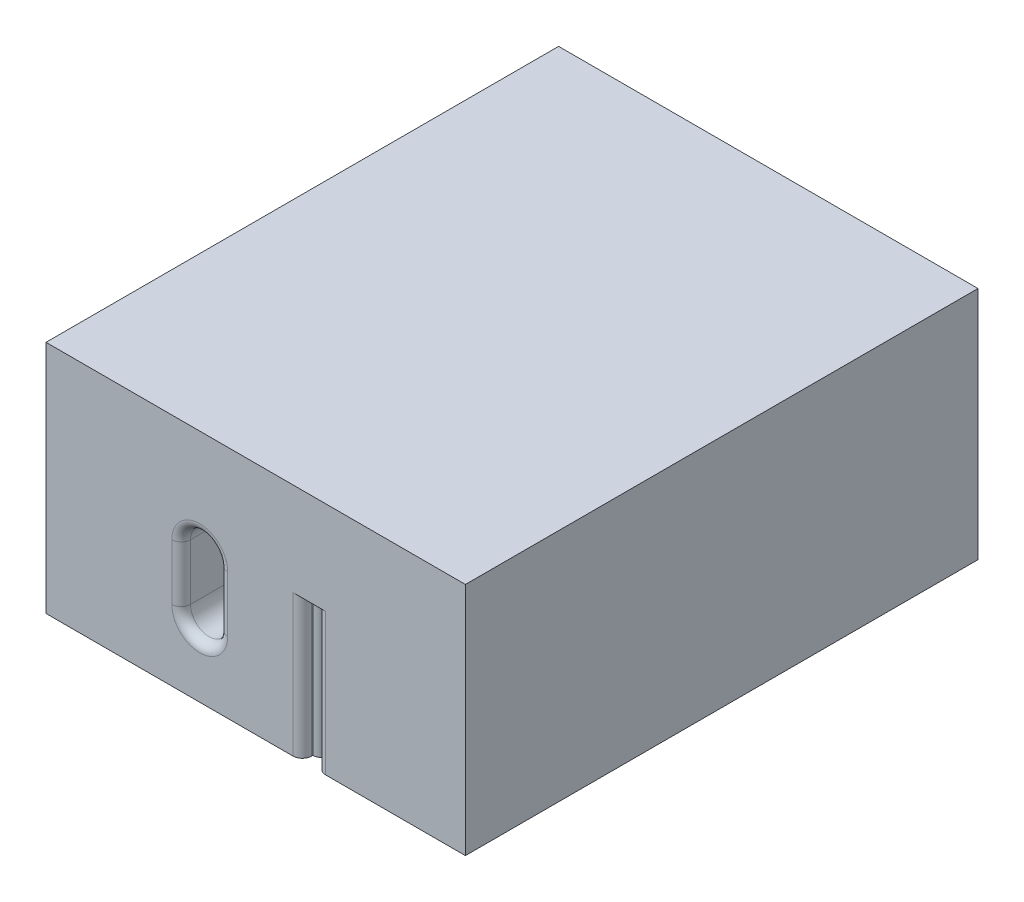
SolidWorks part; units mm, degrees
material "ABS"
ref_plane "Plan de face" through (0, 0, 0) normal (0, 0, 1) x (1, 0, 0)
ref_plane "Plan de dessus" through (0, 0, 0) normal (0, 1, 0) x (1, 0, 0)
ref_plane "Plan de droite" through (0, 0, 0) normal (1, 0, 0) x (0, 0, -1)
sketch "Esquisse1" plane through (0, 0, 0) normal (0, 0, 1) x (1, 0, 0)
  line L0 (0, 0) -> (0, 10) construction
  line L1 (-22.5, -10.6) -> (22.5, -10.6)
  line L2 (-22.5, 14.6) -> (22.5, 14.6)
  line L3 (-15.3167, 7.6) -> (-4, 7.6) construction
  line L4 (-2, 5.6) -> (-2, -5.6) construction
  line L5 (-4, -7.6) -> (-15.3167, -7.6) construction
  line L6 (-6, 3) -> (-6, -3) construction
  line L7 (-4, 3) -> (-4, -3)
  line L8 (-8, 3) -> (-8, -3)
  line L9 (22.5, -10.6) -> (22.5, 14.6)
  line L10 (-22.5, -10.6) -> (-22.5, 14.6)
  arc A4 (-15.6723, 6.7485) -> (-15.6723, -6.7485) centre (-22.5, 0) cw construction
  arc A5 (-15.3167, -7.6) -> (-15.6723, -6.7485) centre (-15.3167, -7.1) cw construction
  arc A6 (-15.3167, 7.6) -> (-15.6723, 6.7485) centre (-15.3167, 7.1) ccw construction
  arc A7 (-2, -5.6) -> (-4, -7.6) centre (-4, -5.6) cw construction
  arc A8 (-4, 7.6) -> (-2, 5.6) centre (-4, 5.6) cw construction
  arc A9 (-4, 3) -> (-8, 3) centre (-6, 3) ccw
  arc A10 (-8, -3) -> (-4, -3) centre (-6, -3) ccw
  point P18 (-16.6348, -7.6)
  point P21 (-16.6348, 7.6)
  point P28 (-6, 0)
  dimension "D2" = 25.2
  dimension "D6" = 7
  dimension "D8" = 0.5
  dimension "D9" = 2
  dimension "D3" = 10
  dimension "D4" = 45
  dimension "D7" = 2
  dimension "D10" = 6
  dimension "D11" = 4
  dimension "D12" = 6
extrude "Boss.-Extru.1" add sketch "Esquisse1" along normal blind 55
sketch "Esquisse3" plane through (0, -10.6, 0) normal (0, -1, 0) x (1, 0, 0)
  line L0 (5, 55) -> (5, 39.4854)
  line L2 (-22.5, 55) -> (22.5, 55) construction
  line L3 (4.4668, 36.6136) -> (0.5332, 26.3864)
  line L4 (0, 23.5146) -> (0, 0)
  line L6 (-22.5, 0) -> (22.5, 0) construction
  line L7 (0, 0) -> (2, 0)
  line L8 (2, 0) -> (2, 17.4387)
  line L9 (2, 19) -> (5, 19) construction
  line L10 (5, 17.4387) -> (5, 0)
  line L11 (5, 0) -> (6.5, 0)
  line L12 (6.5, 0) -> (6.5, 15.5146)
  line L13 (7.0332, 18.3864) -> (10.9668, 28.6136)
  line L14 (11.5, 31.4854) -> (11.5, 55)
  line L15 (11.5, 55) -> (9.5, 55)
  line L16 (9.5, 55) -> (9.5, 37.5613)
  line L17 (9.5, 36) -> (6.5, 36) construction
  line L18 (6.5, 37.5613) -> (6.5, 55)
  line L19 (6.5, 55) -> (5, 55)
  line L20 (22.5, 55) -> (22.5, 0) construction
  line L21 (2.3995, 20.5094) -> (6.1005, 34.4906)
  line L22 (5.3995, 20.5094) -> (9.1005, 34.4906)
  arc A0 (10.9668, 28.6136) -> (11.5, 31.4854) centre (3.5, 31.4854) ccw
  arc A1 (6.5, 15.5146) -> (7.0332, 18.3864) centre (14.5, 15.5146) cw
  arc A2 (0.5332, 26.3864) -> (0, 23.5146) centre (8, 23.5146) ccw
  arc A3 (5, 39.4854) -> (4.4668, 36.6136) centre (-3, 39.4854) cw
  arc A4 (9.5, 37.5613) -> (9.1005, 34.4906) centre (-2.5, 37.5613) cw
  arc A5 (5.3995, 20.5094) -> (5, 17.4387) centre (17, 17.4387) ccw
  arc A6 (2, 17.4387) -> (2.3995, 20.5094) centre (14, 17.4387) cw
  arc A7 (6.1005, 34.4906) -> (6.5, 37.5613) centre (-5.5, 37.5613) ccw
  point P21 (22.5, 27.5)
  point P27 (11.5, 30)
  point P34 (5, 38)
  dimension "D7" = 8
  dimension "D9" = 12
  dimension "D1" = 1.5
  dimension "D2" = 5
  dimension "D3" = 3
  dimension "D4" = 25
  dimension "D5" = 17
  dimension "D6" = 19
  dimension "D8" = 2
extrude "Enlèv. mat.-Extru.1" cut sketch "Esquisse3" against normal offset from surface (15.2 mm away) 10 up to face at (0, 14.6, 27.5)
sketch "Esquisse4" plane through (0, -10.6, 0) normal (0, -1, 0) x (1, 0, 0)
  line L0 (11.5, 31.4854) -> (11.5, 55) construction
  line L1 (9.5, 55) -> (11.5, 55)
  line L2 (9.5, 55) -> (9.5, 43.2427)
  line L3 (9.5, 43.2427) -> (11.5, 43.2427)
  line L4 (11.5, 55) -> (11.5, 43.2427)
  line L5 (2, 17.4387) -> (2, 0) construction
  line L6 (0, 0) -> (2, 0)
  line L7 (0, 0) -> (0, 8.7193)
  line L8 (0, 8.7193) -> (2, 8.7193)
  line L9 (2, 0) -> (2, 8.7193)
extrude "Boss.-Extru.2" add sketch "Esquisse4" against normal up to surface (15.2 mm away) up to face at (3.375, 4.6, 28.8333)
sketch "Esquisse5" plane through (0, -10.6, 0) normal (0, -1, 0) x (1, 0, 0)
  line L0 (5, 39.4854) -> (5, 55) construction
  line L1 (5, 55) -> (5, 39.4854) construction
  line L2 (5, 53.85) -> (5, 53.15)
  line L3 (-22.5, 55) -> (5, 55) construction
  line L4 (5, 51.85) -> (5, 51.15)
  line L5 (5, 49.85) -> (5, 49.15)
  line L6 (5, 47.85) -> (5, 47.15)
  line L7 (5, 45.85) -> (5, 45.15)
  line L8 (5, 43.85) -> (5, 43.15)
  line L9 (5, 41.85) -> (5, 41.15)
  line L10 (5, 39.85) -> (5, 39.15)
  line L11 (-22.5, 27.5) -> (22.5, 27.5) construction
  line L12 (-22.5, 55) -> (-22.5, 0) construction
  line L13 (22.5, 55) -> (22.5, 0) construction
  line L14 (5, 1.15) -> (5, 1.85)
  line L15 (5, 15.15) -> (5, 15.85)
  line L16 (5, 13.15) -> (5, 13.85)
  line L17 (5, 11.15) -> (5, 11.85)
  line L18 (5, 9.15) -> (5, 9.85)
  line L19 (5, 7.15) -> (5, 7.85)
  line L20 (5, 5.15) -> (5, 5.85)
  line L21 (5, 3.15) -> (5, 3.85)
  arc A0 (5, 53.85) -> (5.7, 53.5) centre (5.0904, 53.1559) cw
  arc A1 (5.7, 53.5) -> (5, 53.15) centre (5.0904, 53.8441) cw
  arc A2 (5, 51.85) -> (5.7, 51.5) centre (5.0904, 51.1559) cw
  arc A3 (5.7, 51.5) -> (5, 51.15) centre (5.0904, 51.8441) cw
  arc A4 (5, 49.85) -> (5.7, 49.5) centre (5.0904, 49.1559) cw
  arc A5 (5.7, 49.5) -> (5, 49.15) centre (5.0904, 49.8441) cw
  arc A6 (5, 47.85) -> (5.7, 47.5) centre (5.0904, 47.1559) cw
  arc A7 (5.7, 47.5) -> (5, 47.15) centre (5.0904, 47.8441) cw
  arc A8 (5, 45.85) -> (5.7, 45.5) centre (5.0904, 45.1559) cw
  arc A9 (5.7, 45.5) -> (5, 45.15) centre (5.0904, 45.8441) cw
  arc A10 (5, 43.85) -> (5.7, 43.5) centre (5.0904, 43.1559) cw
  arc A11 (5.7, 43.5) -> (5, 43.15) centre (5.0904, 43.8441) cw
  arc A12 (5, 41.85) -> (5.7, 41.5) centre (5.0904, 41.1559) cw
  arc A13 (5.7, 41.5) -> (5, 41.15) centre (5.0904, 41.8441) cw
  arc A14 (5, 39.85) -> (5.7, 39.5) centre (5.0904, 39.1559) cw
  arc A15 (5.7, 39.5) -> (5, 39.15) centre (5.0904, 39.8441) cw
  arc A16 (5, 1.15) -> (5.7, 1.5) centre (5.0904, 1.8441) ccw
  arc A17 (5.7, 1.5) -> (5, 1.85) centre (5.0904, 1.1559) ccw
  arc A18 (5.7, 15.5) -> (5, 15.85) centre (5.0904, 15.1559) ccw
  arc A19 (5, 15.15) -> (5.7, 15.5) centre (5.0904, 15.8441) ccw
  arc A20 (5.7, 13.5) -> (5, 13.85) centre (5.0904, 13.1559) ccw
  arc A21 (5, 13.15) -> (5.7, 13.5) centre (5.0904, 13.8441) ccw
  arc A22 (5.7, 11.5) -> (5, 11.85) centre (5.0904, 11.1559) ccw
  arc A23 (5, 11.15) -> (5.7, 11.5) centre (5.0904, 11.8441) ccw
  arc A24 (5.7, 9.5) -> (5, 9.85) centre (5.0904, 9.1559) ccw
  arc A25 (5, 9.15) -> (5.7, 9.5) centre (5.0904, 9.8441) ccw
  arc A26 (5.7, 7.5) -> (5, 7.85) centre (5.0904, 7.1559) ccw
  arc A27 (5, 7.15) -> (5.7, 7.5) centre (5.0904, 7.8441) ccw
  arc A28 (5.7, 5.5) -> (5, 5.85) centre (5.0904, 5.1559) ccw
  arc A29 (5, 5.15) -> (5.7, 5.5) centre (5.0904, 5.8441) ccw
  arc A30 (5.7, 3.5) -> (5, 3.85) centre (5.0904, 3.1559) ccw
  arc A31 (5, 3.15) -> (5.7, 3.5) centre (5.0904, 3.8441) ccw
  point P7 (5, 53.5)
  dimension "D4" = 0.7
  dimension "D6" = 2
  dimension "D1" = 0.7
  dimension "D2" = 0.7
  dimension "D3" = 1.5
  dimension "D5" = 8
extrude "Boss.-Extru.3" add sketch "Esquisse5" against normal up to surface (15.2 mm away) up to face at (3.375, 4.6, 30.2866)
fillet "Congé2" radius 1 4 edges at (2, -3, 8.7193) (0, -3, 8.7193) (11.5, -3, 43.2427) (9.5, -3, 43.2427)
fillet "Congé5" radius 1 4 edges at (6.5, -3, 0) (5, -3, 0) (6.5, -3, 55) (5, -3, 55)
fillet "Congé10" radius 1 8 edges at (-6, -5, 0) (-8, 0, 0) (-6, 5, 0) (-6, 5, 55) (-4, 0, 55) (-6, -5, 55) (-4, 0, 0) (-8, 0, 55)
